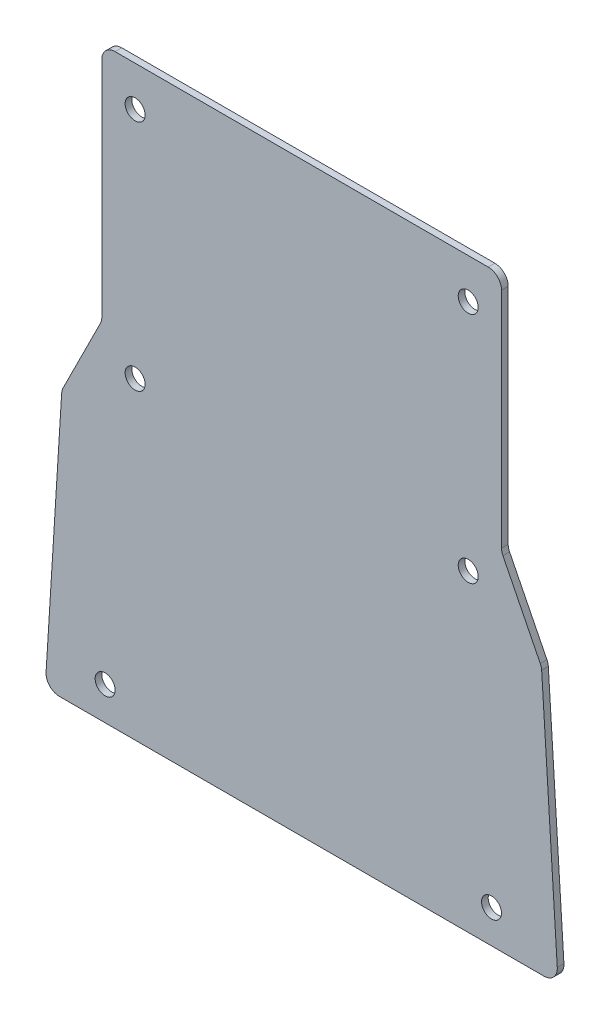
SolidWorks part; units mm, degrees
ref_plane "Front Plane" through (0, 0, 0) normal (0, 0, 1) x (1, 0, 0)
ref_plane "Top Plane" through (0, 0, 0) normal (0, 1, 0) x (1, 0, 0)
ref_plane "Right Plane" through (0, 0, 0) normal (1, 0, 0) x (0, 0, -1)
sketch "Sketch1" plane through (0, 0, 0) normal (0, 0, 1) x (1, 0, 0)
  line L0 (-38.5, 0) -> (38.5, 0)
  line L1 (38.5, 0) -> (36, 40)
  line L2 (36, 40) -> (30, 52)
  line L3 (30, 52) -> (30, 88)
  line L4 (0, 0) -> (0, 97.8089) construction
  line L5 (30, 88) -> (-30, 88)
  line L6 (-30, 52) -> (-30, 88)
  line L7 (-36, 40) -> (-30, 52)
  line L8 (-38.5, 0) -> (-36, 40)
  point P4 (0, 0)
  point P11 (0, 88)
  dimension "D1" = 88
  dimension "D2" = 60
  dimension "D3" = 36
  dimension "D4" = 40
  dimension "D5" = 72
  dimension "D6" = 77
base flange "Base-Flange1" sketch "Sketch1" thickness 1 reverse thickness direction no parameters "D1"=0.7366
fillet "Fillet1" radius 2 8 edges at (36, 40, -0.5) (30, 52, -0.5) (30, 88, -0.5) (-30, 88, -0.5) (-30, 52, -0.5) (-36, 40, -0.5) (-38.5, 0, -0.5) (38.5, 0, -0.5)
sketch "Sketch6" plane through (0, 0, 0) normal (0, 0, 1) x (1, 0, 0)
  line L0 (28, 88) -> (-28, 88) construction
  line L1 (-30, 86) -> (-30, 52.4721) construction
  line L2 (30, 52.4721) -> (30, 86) construction
  line L3 (-36.3711, 0) -> (36.3711, 0) construction
  circle A0 centre (-25, 82) radius 1.5
  circle A1 centre (25, 82) radius 1.5
  circle A2 centre (-25, 47) radius 1.5
  circle A3 centre (25, 47) radius 1.5
  circle A4 centre (-29.5, 5) radius 1.5
  circle A5 centre (28.5, 5) radius 1.5
  dimension "D1" = 3
  dimension "D2" = 6
  dimension "D3" = 5
  dimension "D4" = 5
  dimension "D5" = 3
  dimension "D6" = 50
  dimension "D7" = 5
  dimension "D8" = 41
  dimension "D9" = 58
  dimension "D11" = 28.5
  dimension "D10" = 5
extrude "Cut-Extrude1" cut sketch "Sketch6" against normal through all normal cut yes
sketch "Bend-Lines1" [suppressed] plane through (0, 0, 0) normal (0, 1, 0) x (1, 0, 0)
sketch "Bounding-Box1" [suppressed] plane through (0, 0, 0) normal (0, 1, 0) x (1, 0, 0)
sheet metal parameters "Sheet-Metal1" thickness 1 parameters "D1"=0.7366
flat pattern "Flat-Pattern1" [suppressed]
sketch "Bend-Lines2" plane through (0, 0, 0) normal (0, 1, 0) x (1, 0, 0)
sketch3d "Bounding-Box2" [suppressed]
  line L0 (38.3707, 0, 0) -> (38.3707, 88, 0) construction
  line L1 (-38.3709, 0, 0) -> (-38.3709, 88, 0) construction
  line L2 (38.3707, 0, 0) -> (-38.3709, 0, 0) construction
  line L3 (38.3707, 88, 0) -> (-38.3709, 88, 0) construction
sheet metal parameters "Sheet-Metal2" thickness 1 parameters "D1"=0.7366
flat pattern "Flat-Pattern1"
sketch "Bend-Lines2" plane through (0, 0, 0) normal (0, 1, 0) x (1, 0, 0)
sketch3d "Bounding-Box2" [suppressed]
  line L0 (38.3707, 0, 0) -> (38.3707, 88, 0) construction
  line L1 (-38.3709, 0, 0) -> (-38.3709, 88, 0) construction
  line L2 (38.3707, 0, 0) -> (-38.3709, 0, 0) construction
  line L3 (38.3707, 88, 0) -> (-38.3709, 88, 0) construction
